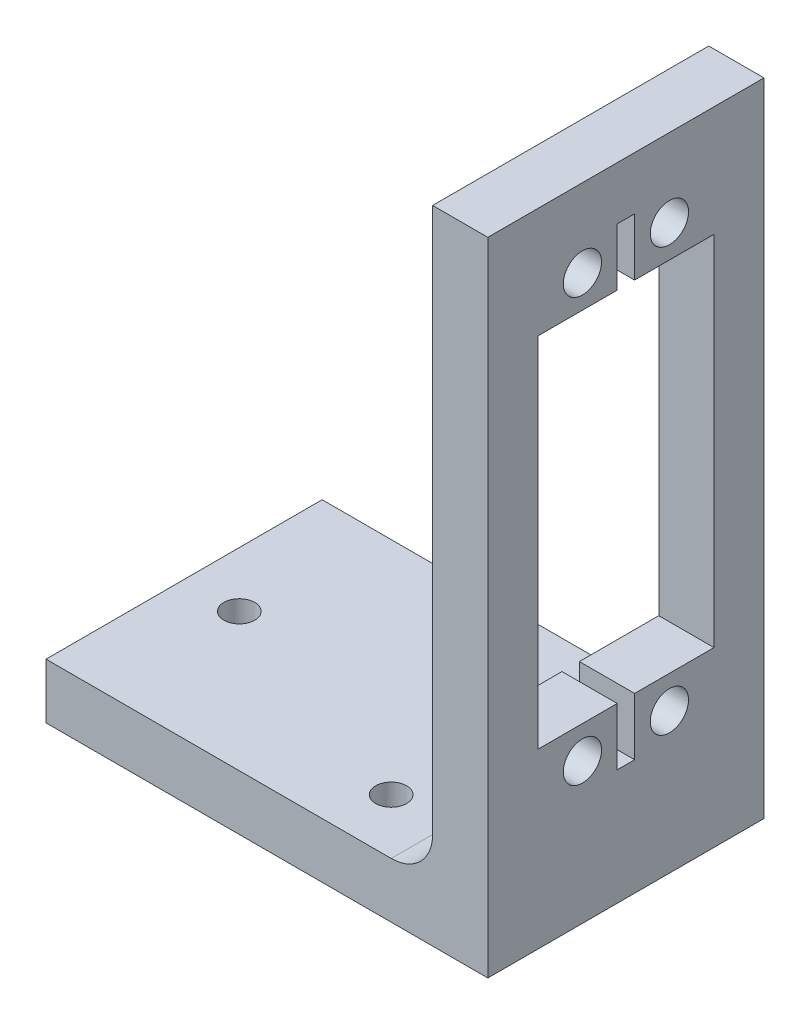
SolidWorks part; units mm, degrees
ref_plane "Front Plane" through (0, 0, 0) normal (0, 0, 1) x (1, 0, 0)
ref_plane "Top Plane" through (0, 0, 0) normal (0, 1, 0) x (1, 0, 0)
ref_plane "Right Plane" through (0, 0, 0) normal (1, 0, 0) x (0, 0, -1)
sketch "Sketch3" plane through (0, 0, 0) normal (1, 0, 0) x (0, 0, -1)
  line L0 (5.748, 54.704) -> (26.002, 13.55) construction
  line L1 (0, 0) -> (31.75, 0)
  line L2 (0, 0) -> (0, 67.404)
  line L3 (0, 67.404) -> (31.75, 67.404)
  line L4 (31.75, 0) -> (31.75, 67.404)
  line L5 (5.748, 54.704) -> (14.875, 54.704)
  line L6 (5.748, 54.704) -> (5.748, 13.55)
  line L7 (5.748, 13.55) -> (14.875, 13.55)
  line L8 (26.002, 54.704) -> (26.002, 13.55)
  line L9 (26.002, 54.704) -> (5.748, 13.55) construction
  line L10 (10.875, 58.427) -> (20.875, 9.827) construction
  line L11 (10.875, 9.827) -> (20.875, 58.427) construction
  line L12 (16.875, 13.55) -> (26.002, 13.55)
  line L13 (14.875, 13.55) -> (14.875, 6.946)
  line L14 (14.875, 6.946) -> (16.875, 6.946)
  line L15 (16.875, 13.55) -> (16.875, 6.946)
  line L16 (15.875, 34.127) -> (-939.9401, 34.127) construction
  line L17 (14.875, 61.308) -> (16.875, 61.308)
  line L18 (14.875, 54.704) -> (14.875, 61.308)
  line L19 (16.875, 54.704) -> (16.875, 61.308)
  line L20 (16.875, 54.704) -> (26.002, 54.704)
  circle A0 centre (10.875, 9.827) radius 2.2
  circle A1 centre (20.875, 9.827) radius 2.2
  circle A2 centre (10.875, 58.427) radius 2.2
  circle A3 centre (20.875, 58.427) radius 2.2
  point P13 (15.875, 6.946)
  point P22 (15.875, 34.127)
  point P23 (15.875, 34.127)
  point P32 (15.875, 44.45)
  point P33 (60.8535, 71.879)
  point P34 (15.875, 0)
  dimension "D3" = 4.4
  dimension "D1" = 10
  dimension "D2" = 48.6
  dimension "D4" = 41.154
  dimension "D5" = 20.254
  dimension "D6" = 2
  dimension "D7" = 6.604
  dimension "D8" = 30.9
  dimension "D9" = 44.45
  dimension "D10" = 31.75
  dimension "D12" = 12.7
extrude "Boss-Extrude1" add sketch "Sketch3" along normal blind 6.35
sketch "Sketch5" plane through (6.35, 0, 0) normal (1, 0, 0) x (0, 0, -1)
  line L1 (0, 0) -> (31.75, 0)
  line L2 (0, 0) -> (0, -6.35)
  line L3 (0, -6.35) -> (31.75, -6.35)
  line L4 (31.75, 0) -> (31.75, -6.35)
  point P5 (0, 0)
  dimension "D1" = 6.35
extrude "Boss-Extrude2" add sketch "Sketch5" against normal blind 50.8
fillet "Fillet1" radius 4.7625 1 edges at (0, 0, -15.875)
sketch "Sketch6" plane through (0, 0, 0) normal (0, 1, 0) x (1, 0, 0)
  line L0 (-44.45, 0) -> (-4.7625, 0) construction
  line L1 (-4.7625, 0) -> (-4.7625, 31.75) construction
  line L2 (-44.45, 31.75) -> (-44.45, 0) construction
  line L3 (0, 15.875) -> (-33.0413, 15.875) construction
  line L4 (0, 31.75) -> (0, 0) construction
  circle A0 centre (-11.1125, 6.35) radius 1.777
  circle A2 centre (-38.1, 15.875) radius 1.777
  circle A3 centre (-11.1125, 25.4) radius 1.777
  point P16 (0, 0)
  point P17 (0, 0)
  point P18 (0, 0)
  dimension "D1" = 3.554
  dimension "D2" = 6.35
  dimension "D3" = 6.35
  dimension "D4" = 6.35
extrude "Cut-Extrude1" cut sketch "Sketch6" against normal through all
equation "\"D1@Sketch6\" = 3.3mm + \"normTol\""
equation "\"tightTol\"= 0.005in"
equation "\"normTol\"= 0.01in"
equation "\"looseTol\"= 0.02in"
